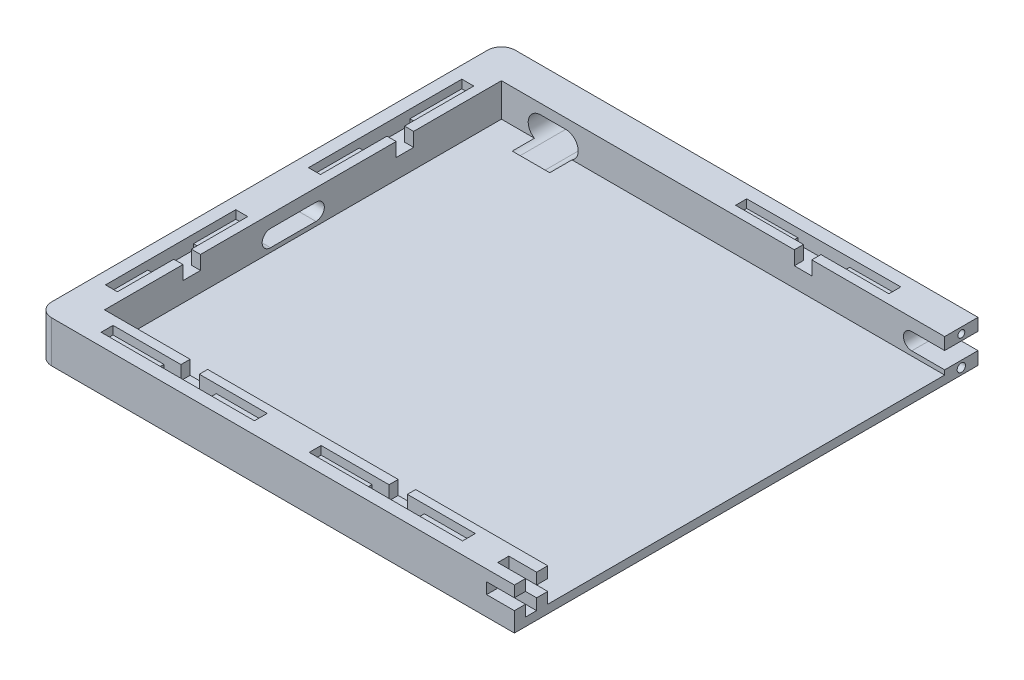
SolidWorks part; units mm, degrees
ref_plane "Front Plane" through (0, 0, 0) normal (0, 0, 1) x (1, 0, 0)
ref_plane "Top Plane" through (0, 0, 0) normal (0, 1, 0) x (1, 0, 0)
ref_plane "Right Plane" through (0, 0, 0) normal (1, 0, 0) x (0, 0, -1)
sketch "Sketch1" plane through (0, 0, 0) normal (0, 1, 0) x (1, 0, 0)
  line L0 (-131.0313, 0) -> (139.9056, 0) construction
  line L1 (0, 71.4375) -> (-159.54, 71.4375)
  line L2 (0, 215.1028) -> (0, -153.2812) construction
  line L3 (-159.54, 71.4375) -> (-159.54, -71.4375)
  line L4 (-159.54, -71.4375) -> (0, -71.4375)
  line L5 (0, 71.4375) -> (0, -71.4375)
  point P9 (0, 0)
  dimension "D1" = 159.54
  dimension "D2" = 142.875
extrude "Boss-Extrude1" add sketch "Sketch1" along normal blind 3
sketch "Sketch2" plane through (0, 0, 0) normal (0, 1, 0) x (1, 0, 0)
  line L0 (-224.2217, 0) -> (91.1792, 0) construction
  line L1 (0, 149.3369) -> (0, -151.0656) construction
  line L2 (0, 71.4375) -> (0, 83.4375)
  line L3 (0, 83.4375) -> (-171.54, 83.4375)
  line L4 (-171.54, 83.4375) -> (-171.54, -83.4375)
  line L5 (-171.54, -83.4375) -> (0, -83.4375)
  line L6 (0, -83.4375) -> (0, -71.4375)
  line L8 (-159.54, 71.4375) -> (-159.54, -71.4375) construction
  line L13 (0, -71.4375) -> (0, 71.4375)
  line L14 (0, 71.4375) -> (-159.54, 71.4375)
  line L15 (-159.54, 71.4375) -> (-159.54, -71.4375)
  line L16 (-159.54, -71.4375) -> (0, -71.4375)
  line L18 (0, 71.4375) -> (-159.54, 71.4375)
  line L19 (-159.54, 71.4375) -> (-159.54, -71.4375)
  line L20 (-159.54, -71.4375) -> (0, -71.4375)
  dimension "D1" = 12
  dimension "D2" = 12
  dimension "D3" = 12
  dimension "D4" = 0
extrude "Boss-Extrude2" add sketch "Sketch2" along normal blind 15
sketch "Sketch3" plane through (0, 15, 0) normal (0, 1, 0) x (1, 0, 0)
  line L0 (-159.54, 71.4375) -> (-159.54, 39.8375) construction
  line L1 (-159.54, -71.4375) -> (-159.54, 71.4375) construction
  line L2 (-159.54, -71.4375) -> (-159.54, -43.1875) construction
  line L3 (-159.54, 39.8375) -> (-159.54, 33.5375)
  line L4 (-159.54, 39.8375) -> (-162.84, 39.8375)
  line L5 (-159.54, 33.5375) -> (-162.84, 33.5375)
  line L6 (-162.84, 39.8375) -> (-162.84, 64.7884)
  line L7 (-162.84, 33.5375) -> (-162.84, 9.5884)
  line L8 (-162.84, 64.7884) -> (-167.14, 64.7884)
  line L9 (-167.14, 64.7884) -> (-167.14, 9.5884)
  line L10 (-167.14, 9.5884) -> (-162.84, 9.5884)
  line L11 (-159.54, 71.4375) -> (-159.54, -71.4375) construction
  line L12 (-23.07, -74.4375) -> (-47.52, -74.4375)
  line L13 (-159.54, -36.8875) -> (-159.54, -43.1875)
  line L14 (-159.54, -36.8875) -> (-162.84, -36.8875)
  line L15 (-159.54, -43.1875) -> (-162.84, -43.1875)
  line L16 (-162.84, -36.8875) -> (-162.84, -16.5875)
  line L17 (-162.84, -16.5875) -> (-167.14, -16.5875)
  line L18 (-167.14, -16.5875) -> (-167.14, -63.4875)
  line L19 (-167.14, -63.4875) -> (-162.84, -63.4875)
  line L20 (-162.84, -63.4875) -> (-162.84, -43.1875)
  line L21 (-23.07, -79.0375) -> (-23.07, -74.4375)
  line L22 (-78.27, -79.0375) -> (-23.07, -79.0375)
  line L23 (-78.27, -74.7375) -> (-78.27, -79.0375)
  line L24 (-53.82, -74.7375) -> (-78.27, -74.7375)
  line L25 (-53.82, -71.4375) -> (-53.82, -74.7375)
  line L26 (-47.52, -71.4375) -> (-53.82, -71.4375)
  line L27 (-47.52, -74.4375) -> (-47.52, -71.4375)
  line L28 (-97.97, -79.0375) -> (-97.97, -74.4375)
  line L29 (-153.17, -79.0375) -> (-97.97, -79.0375)
  line L30 (-153.17, -74.7375) -> (-153.17, -79.0375)
  line L31 (-128.72, -74.7375) -> (-153.17, -74.7375)
  line L32 (-128.72, -71.4375) -> (-128.72, -74.7375)
  line L33 (-122.42, -71.4375) -> (-128.72, -71.4375)
  line L34 (-122.42, -74.4375) -> (-122.42, -71.4375)
  line L35 (-97.97, -74.4375) -> (-122.42, -74.4375)
  line L36 (0, -71.4375) -> (-159.54, -71.4375) construction
  line L37 (-159.54, -71.4375) -> (0, -71.4375) construction
  line L38 (-47.82, 74.7375) -> (-47.82, 71.4375)
  line L39 (-23.37, 74.7375) -> (-47.82, 74.7375)
  line L40 (-23.3708, 79.0375) -> (-23.37, 74.7375)
  line L41 (-78.57, 78.7359) -> (-23.3708, 79.0375)
  line L42 (-78.57, 74.7359) -> (-78.57, 78.7359)
  line L43 (-54.12, 74.7359) -> (-78.57, 74.7359)
  line L44 (-54.12, 71.4375) -> (-54.12, 74.7359)
  line L45 (-47.82, 71.4375) -> (-54.12, 71.4375)
  line L46 (-159.54, 71.4375) -> (0, 71.4375) construction
  dimension "D1" = 31.6
  dimension "D2" = 55.2
  dimension "D3" = 6.3
  dimension "D4" = 3.3
  dimension "D5" = 6.3
  dimension "D6" = 20.3
  dimension "D7" = 4.3
  dimension "D8" = 4.3
  dimension "D9" = 28.25
  dimension "D10" = 3.3
  dimension "D11" = 30.82
  dimension "D12" = 6.3
  dimension "D13" = 3.3
  dimension "D14" = 4.3
  dimension "D15" = 55.2
  dimension "D16" = 68.6
  dimension "D17" = 6.3
  dimension "D18" = 3.3
  dimension "D19" = 4.3
  dimension "D20" = 55.2
  dimension "D21" = 6.3
  dimension "D22" = 3.3
  dimension "D23" = 4.3
  dimension "D24" = 55.2
  dimension "D25" = 47.82
extrude "Cut-Extrude1" cut sketch "Sketch3" against normal blind 3
sketch "Sketch4" plane through (0, 12, 0) normal (0, 1, 0) x (1, 0, 0)
  line L0 (-54.12, 74.7359) -> (-54.12, 71.4375)
  line L1 (-54.12, 71.4375) -> (-47.82, 71.4375)
  line L2 (-47.82, 71.4375) -> (-47.82, 74.7375)
  line L3 (-47.82, 74.7375) -> (-35.595, 74.7375) construction
  line L4 (-128.72, -74.7375) -> (-140.945, -74.7375) construction
  line L5 (-54.12, 74.7359) -> (-66.345, 74.7359) construction
  line L6 (-78.57, 74.7359) -> (-54.12, 74.7359) construction
  line L7 (-47.82, 74.7375) -> (-23.37, 74.7375) construction
  line L8 (-54.12, 74.7359) -> (-60.2325, 74.7359)
  line L14 (-47.82, 74.7375) -> (-41.7075, 74.7375)
  line L15 (-159.54, 39.8375) -> (-159.54, 33.5375)
  line L16 (-159.54, 33.5375) -> (-162.84, 33.5375)
  line L17 (-162.84, 39.8375) -> (-162.84, 52.313) construction
  line L18 (-162.84, 39.8375) -> (-162.84, 64.7884) construction
  line L19 (-162.84, 33.5375) -> (-162.84, 21.563) construction
  line L20 (-162.84, 9.5884) -> (-162.84, 33.5375) construction
  line L21 (-159.54, 39.8375) -> (-162.84, 39.8375)
  line L24 (-128.72, -74.7375) -> (-153.17, -74.7375) construction
  line L26 (-122.42, -74.4375) -> (-110.195, -74.4375) construction
  line L30 (-162.84, 39.8375) -> (-162.84, 46.0752)
  line L31 (-162.84, 46.0752) -> (-167.14, 46.0752)
  line L32 (-167.14, 64.7884) -> (-167.14, 9.5884) construction
  line L33 (-167.14, 46.0752) -> (-167.14, 27.8502)
  line L34 (-167.14, 64.7884) -> (-167.14, 9.5884) construction
  line L35 (-167.14, 27.8502) -> (-162.84, 27.8502)
  line L36 (-162.84, 27.8502) -> (-162.84, 33.5375)
  line L37 (-162.84, -36.8875) -> (-162.84, -26.7375) construction
  line L38 (-162.84, -36.8875) -> (-162.84, -16.5875) construction
  line L39 (-167.14, -31.8125) -> (-167.14, -48.2625)
  line L40 (-162.84, -63.4875) -> (-162.84, -43.1875) construction
  line L41 (-162.84, -31.8125) -> (-167.14, -31.8125)
  line L42 (-167.14, -16.5875) -> (-167.14, -63.4875) construction
  line L43 (-162.84, -43.1875) -> (-162.84, -53.3375) construction
  line L44 (-167.14, -48.2625) -> (-162.84, -48.2625)
  line L45 (-162.84, -48.2625) -> (-162.84, -43.1875)
  line L46 (-162.84, -43.1875) -> (-159.54, -43.1875)
  line L47 (-159.54, -43.1875) -> (-159.54, -36.8875)
  line L48 (-159.54, -36.8875) -> (-162.84, -36.8875)
  line L49 (-162.84, -36.8875) -> (-162.84, -31.8125)
  line L50 (-97.97, -74.4375) -> (-122.42, -74.4375) construction
  line L51 (-128.72, -71.4375) -> (-128.72, -74.7375)
  line L52 (-128.72, -74.7375) -> (-134.8325, -74.7375)
  line L53 (-134.8325, -74.7375) -> (-134.8325, -79.0375)
  line L54 (-153.17, -79.0375) -> (-97.97, -79.0375) construction
  line L55 (-134.8325, -79.0375) -> (-116.3075, -79.0375)
  line L56 (-116.3075, -79.0375) -> (-116.3075, -74.4375)
  line L59 (-122.42, -71.4375) -> (-128.72, -71.4375)
  line L60 (-122.42, -71.4375) -> (-122.42, -74.4375)
  line L61 (-122.42, -74.4375) -> (-116.3075, -74.4375)
  line L62 (-53.82, -74.7375) -> (-66.045, -74.7375) construction
  line L63 (-53.82, -74.7375) -> (-78.27, -74.7375) construction
  line L64 (-47.52, -74.4375) -> (-35.295, -74.4375) construction
  line L65 (-23.07, -74.4375) -> (-47.52, -74.4375) construction
  line L66 (-53.82, -74.7375) -> (-59.9325, -74.7375)
  line L67 (-59.9325, -74.7375) -> (-59.9325, -79.0375)
  line L68 (-78.27, -79.0375) -> (-23.07, -79.0375) construction
  line L69 (-59.9325, -79.0375) -> (-41.4075, -79.0375)
  line L70 (-41.4075, -79.0375) -> (-41.4075, -74.4375)
  line L71 (-41.4075, -74.4375) -> (-47.52, -74.4375)
  line L72 (-47.52, -74.4375) -> (-47.52, -71.4375)
  line L73 (-47.52, -71.4375) -> (-53.82, -71.4375)
  line L74 (-53.82, -71.4375) -> (-53.82, -74.7375)
  line L75 (-41.7075, 74.7375) -> (-41.7075, 78.9373)
  line L76 (-23.3708, 79.0375) -> (-78.57, 78.7359) construction
  line L77 (-41.7075, 78.9373) -> (-60.2325, 78.8361)
  line L78 (-23.3708, 79.0375) -> (-78.57, 78.7359) construction
  line L79 (-60.2325, 78.8361) -> (-60.2325, 74.7359)
extrude "Cut-Extrude2" cut sketch "Sketch4" against normal blind 2
sketch "Sketch5" plane through (-171.54, 0, 0) normal (-1, 0, 0) x (0, 0, 1)
  line L0 (0, 7.5) -> (32.6582, 7.5) construction
  line L1 (-83.4375, 7.5) -> (0, 7.5) construction
  line L2 (-83.4375, 15) -> (-83.4375, 0) construction
  line L3 (-83.4375, 11.8257) -> (-7.6875, 11.8257) construction
  line L4 (-4.6875, 10.5) -> (11.6925, 10.5)
  line L5 (-4.6875, 4.5) -> (11.6925, 4.5)
  line L8 (-7.6875, 4.845) -> (-7.6875, 10.155) construction
  arc A0 (-4.6875, 4.5) -> (-4.6875, 10.5) centre (-4.6875, 7.5) cw
  arc A1 (11.6925, 10.5) -> (11.6925, 4.5) centre (11.6925, 7.5) cw
  point P17 (-4.6875, 10.5)
  point P21 (-7.6875, 7.5)
  dimension "D2" = 3
  dimension "D1" = 16.38
  dimension "D3" = 75.75
extrude "Cut-Extrude3" cut sketch "Sketch5" against normal blind 12
sketch "Sketch7" plane through (0, 0, -83.4375) normal (0, 0, -1) x (-1, 0, 0)
  line L0 (60.062, 7.6343) -> (-60.062, 7.6343) construction
  line L1 (0, 0) -> (171.54, 0) construction
  line L2 (14.8425, 7.6343) -> (14.8425, 12.6467) construction
  line L3 (-4.5375, 10.6343) -> (11.8425, 10.6343)
  line L4 (-4.5375, 4.6343) -> (11.8425, 4.6343)
  line L5 (0, 11.4722) -> (14.8425, 11.4722) construction
  line L6 (0, 15) -> (0, 0) construction
  arc A0 (-4.5375, 4.6343) -> (-4.5375, 10.6343) centre (-4.5375, 7.6343) cw
  arc A1 (11.8425, 10.6343) -> (11.8425, 4.6343) centre (11.8425, 7.6343) cw
  point P3 (0, 7.6343)
  dimension "D3" = 3
  dimension "D1" = 14.8425
  dimension "D2" = 16.38
  dimension "D4" = 7.6343
extrude "Cut-Extrude5" cut sketch "Sketch7" against normal blind 12
sketch "Sketch8" plane through (0, 0, -83.4375) normal (0, 0, -1) x (-1, 0, 0)
  line L0 (171.54, 7.5) -> (143.1877, 7.5) construction
  line L1 (171.54, 15) -> (171.54, 0) construction
  line L2 (171.54, 7.9) -> (145.4, 7.9) construction
  line L3 (145.4, 7.9) -> (136.4, 7.9) construction
  line L4 (0, 15) -> (171.54, 15) construction
  line L5 (136.4, 11.4) -> (145.4, 11.4)
  line L6 (136.4, 2.4) -> (145.4, 2.4)
  line L7 (164.2575, 6.9) -> (140.1095, 6.9) construction
  line L8 (140.9, 7.9) -> (140.9, 5.9) construction
  line L9 (145.4, 7.9) -> (145.4, 15.4665) construction
  arc A0 (136.4, 2.4) -> (136.4, 11.4) centre (136.4, 6.9) cw
  arc A1 (145.4, 11.4) -> (145.4, 2.4) centre (145.4, 6.9) cw
  point P19 (140.9, 6.9)
  dimension "D5" = 9
  dimension "D1" = 26.14
  dimension "D2" = 9
  dimension "D3" = 7.1
  dimension "D4" = 9
  dimension "D6" = 1
  dimension "2" = 2
extrude "Cut-Extrude6" cut sketch "Sketch8" against normal blind 20
sketch "Sketch9" plane through (-159.54, 0, 0) normal (1, 0, 0) x (0, 0, -1)
  line L0 (0, 4.5) -> (0, 3) construction
  line L1 (4.6875, 4.5) -> (-11.6925, 4.5) construction
  line L2 (71.4375, 3) -> (-71.4375, 3) construction
  line L3 (36.6875, 10) -> (36.6875, 3) construction
  line L4 (33.5375, 10) -> (39.8375, 10) construction
sketch "Sketch10" plane through (0, 0, 0) normal (1, 0, 0) x (0, 0, -1)
  line L0 (-71.4375, 3) -> (-71.4375, 15) construction
  line L1 (-71.4375, 15) -> (-83.4375, 15) construction
  line L2 (-83.4375, 15) -> (-83.4375, 3) construction
  line L3 (-83.4375, 15) -> (-83.4375, 0) construction
  line L4 (-83.4375, 3) -> (-71.4375, 3) construction
  line L5 (-71.4375, 3) -> (-83.4375, 15) construction
  line L6 (-83.4375, 15) -> (-71.4375, 15) construction
  line L7 (-71.4375, 15) -> (-83.4375, 3) construction
  line L8 (-77.4375, 15.3824) -> (-77.4375, 3) construction
  line L9 (-83.4375, 9) -> (-71.292, 9) construction
  line L10 (-79.4375, 15) -> (-75.4375, 15)
  line L11 (-71.4375, 7) -> (-71.4375, 11)
  line L12 (-75.4375, 3) -> (-79.4375, 3)
  line L13 (-83.4375, 7) -> (-83.4375, 11)
  line L14 (-79.4375, 15) -> (-79.4375, 11)
  line L15 (-79.4375, 11) -> (-83.4375, 11)
  line L16 (-83.4375, 7) -> (-79.4375, 7)
  line L17 (-79.4375, 7) -> (-79.4375, 3)
  line L18 (-75.4375, 3) -> (-75.4375, 7)
  line L19 (-75.4375, 7) -> (-71.4375, 7)
  line L20 (-71.4375, 11) -> (-75.4375, 11)
  line L21 (-75.4375, 11) -> (-75.4375, 15)
  line L22 (-77.4375, 9) -> (-77.4375, 15) construction
  line L23 (-71.4375, 9) -> (-83.4375, 9) construction
  point P15 (-77.4375, 15)
  point P19 (-71.4375, 9)
  point P22 (-77.4375, 3)
  point P25 (-83.4375, 9)
  dimension "D1" = 4
  dimension "D2" = 4
  dimension "D3" = 4
  dimension "D4" = 4
  dimension "D5" = 0
extrude "Cut-Extrude8" cut sketch "Sketch10" against normal blind 10
fillet "Fillet2" radius 5 1 edges at (-171.54, 7.5, 83.4375)
fillet "Fillet3" radius 5 1 edges at (-171.54, 7.5, -83.4375)
sketch "Sketch11" plane through (0, 0, 0) normal (1, 0, 0) x (0, 0, -1)
  line L0 (71.4375, 4.6343) -> (83.4375, 4.6343) construction
  line L1 (71.4375, 4.6343) -> (71.4375, 0) construction
  line L2 (-83.4375, 0) -> (83.4375, 0) construction
  line L3 (71.4375, 0) -> (83.4375, 0) construction
  line L4 (83.4375, 0) -> (83.4375, 4.6343) construction
  line L5 (77.4375, 4.6343) -> (77.4375, 0) construction
  line L6 (71.4375, 2.3172) -> (83.4375, 2.3172) construction
  line L7 (71.4375, 15) -> (71.4375, 10.6343) construction
  line L8 (71.4375, 10.6343) -> (83.4375, 10.6343) construction
  line L9 (83.4375, 10.6343) -> (83.4375, 15) construction
  line L10 (83.4375, 15) -> (71.4375, 15) construction
  line L11 (71.4375, 15) -> (77.4375, 15) construction
  line L12 (77.4375, 15) -> (77.4375, 10.6343) construction
  line L13 (77.4375, 10.6343) -> (71.4375, 10.6343) construction
  line L14 (71.4375, 10.6343) -> (71.4375, 12.8172) construction
  line L15 (71.4375, 12.8172) -> (83.4375, 12.8172) construction
  circle A0 centre (77.4375, 2.3172) radius 1.5
  circle A1 centre (77.4375, 12.8172) radius 1.25
  dimension "D1" = 3
  dimension "D2" = 2.5
extrude "Cut-Extrude9" cut sketch "Sketch11" against normal blind 10
